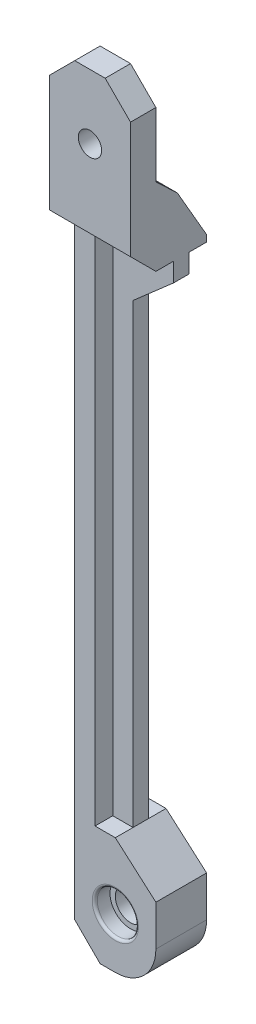
SolidWorks part; units mm, degrees
ref_plane "前视基准面" through (0, 0, 0) normal (0, 0, 1) x (1, 0, 0)
ref_plane "上视基准面" through (0, 0, 0) normal (0, 1, 0) x (1, 0, 0)
ref_plane "右视基准面" through (0, 0, 0) normal (1, 0, 0) x (0, 0, -1)
other "Configuration Table"
sketch "草图1" plane through (0, 0, 0) normal (0, 0, 1) x (1, 0, 0)
  line L0 (0, 96.354) -> (0, 70.2446) construction
  line L1 (-8, -77.5) -> (8, -77.5)
  line L2 (-8, -77.5) -> (-8, -61.5)
  line L4 (8, -77.5) -> (8, -61.5)
  line L5 (-8, -77.5) -> (5.9355, 57.5) construction
  line L6 (-5.9355, 57.5) -> (8, -77.5) construction
  line L7 (-8, 57.5) -> (8, 57.5)
  line L8 (0, 62.7554) -> (0, 49.1197) construction
  line L12 (0, 35.5101) -> (8, 42.5)
  line L13 (0, -54.4899) -> (0, 35.5101)
  line L14 (8, -61.5) -> (0, -54.4899)
  line L15 (-8, 42.5) -> (-8, 57.5)
  line L16 (8, 42.5) -> (8, 57.5)
  line L17 (-8, 42.5) -> (-8, -61.5)
  circle A1 centre (0, -67.5) radius 4.05
  point P0 (0, 0)
  dimension "D4" = 8.1
  dimension "D1" = 110
  dimension "D2" = 8
  dimension "D3" = 10
  dimension "D5" = 16
  dimension "D6" = 16
  dimension "D7" = 15
extrude "凸台-拉伸1" add sketch "草图1" along normal blind 10
sketch "草图2" plane through (0, 0, 10) normal (0, 0, 1) x (1, 0, 0)
  line L0 (-8, 51.2197) -> (8, 51.2197)
  line L1 (8, 51.2197) -> (8, 79.2039)
  line L2 (8, 79.2039) -> (-8, 79.2039)
  line L3 (-8, 79.2039) -> (-8, 51.2197)
  line L4 (-8, 57.5) -> (-8, -77.5) construction
  dimension "D1" = 16
  dimension "D2" = 0
extrude "凸台-拉伸2" add sketch "草图2" along normal blind 5
sketch "草图3" plane through (0, 0, 15) normal (0, 0, 1) x (1, 0, 0)
  circle A0 centre (0, 66.5) radius 2.3
  circle A1 centre (0, -67.5) radius 4.0186 construction
  dimension "D2" = 4.6
  dimension "D1" = 134
extrude "切除-拉伸1" cut sketch "草图3" against normal blind 5
chamfer "倒角2" distance 5 angle 45 1 edges at (0, 51.2197, 10)
chamfer "倒角3" distance 10 angle 30 1 edges at (0, 57.5, 0) first distance on face at (2, -9.7475, 0)
sketch "草图4" plane through (0, 0, 0) normal (1, 0, 0) x (0, 0, -1)
  line L0 (-10, 61.5) -> (-5.7735, 57.5)
  line L1 (-10, 57.5) -> (-10, 79.2039) construction
  line L2 (-10, 57.5) -> (-5.7735, 57.5) construction
  dimension "D1" = 4
sketch "草图5" plane through (8, 0, 0) normal (1, 0, 0) x (0, 0, -1)
  line L0 (-10, 61.5) -> (-5.7735, 57.5)
  line L1 (-5.7735, 57.5) -> (-10, 57.5)
  line L2 (-10, 57.5) -> (-10, 61.5)
extrude "凸台-拉伸3" add sketch "草图5" against normal blind 3
mirror "镜向1" about plane through (0, 0, 0) normal (1, 0, 0) of "凸台-拉伸3"
chamfer "倒角5" distance 5 angle 45 2 edges at (-8, 79.2039, 12.5) (8, 79.2039, 12.5)
chamfer "倒角6" distance 5 angle 45 1 edges at (-8, -77.5, 5)
fillet "圆角1" radius 8 1 edges at (8, -77.5, 5)
sketch "草图7" plane through (0, 0, 0) normal (1, 0, 0) x (0, 0, -1)
  line L0 (-5, 35.5101) -> (-5, 2.2635) construction
  line L11 (0, 42.5) -> (0, 47.5) construction
  line L12 (0, 46.2197) -> (-3.5, 46.2197)
  line L13 (0, 46.2197) -> (0, -54.4899)
  line L14 (0, -54.4899) -> (-3.5, -54.4899)
  line L15 (-3.5, 46.2197) -> (-3.5, -54.4899)
  line L16 (-10, -54.4899) -> (0, -54.4899) construction
  line L17 (-10, -54.4899) -> (-6.5, -54.4899)
  line L18 (-6.5, 46.2197) -> (-6.5, -54.4899)
  line L19 (-10, 46.2197) -> (-6.5, 46.2197)
  line L20 (-10, 46.2197) -> (-10, -54.4899)
  line L21 (-10, 42.5) -> (-10, 46.2197) construction
  dimension "D1" = 3.5
extrude "切除-拉伸3" cut sketch "草图7" against normal blind 4 and the other way blind 20
ref_plane "基准面1" through (0, 0, 5) normal (0, 0, 1) x (1, 0, 0)
sketch "草图8" plane through (0, 0, 5) normal (0, 0, 1) x (1, 0, 0)
  circle A0 centre (0, -67.5) radius 3
  circle A1 centre (0, -67.5) radius 4.05
  dimension "D1" = 6
extrude "凸台-拉伸4" add sketch "草图8" along normal blind 2 and the other way blind 2
fillet "圆角2" radius 0.5 2 edges at (4.05, -67.5, 10) (4.05, -67.5, 0)
